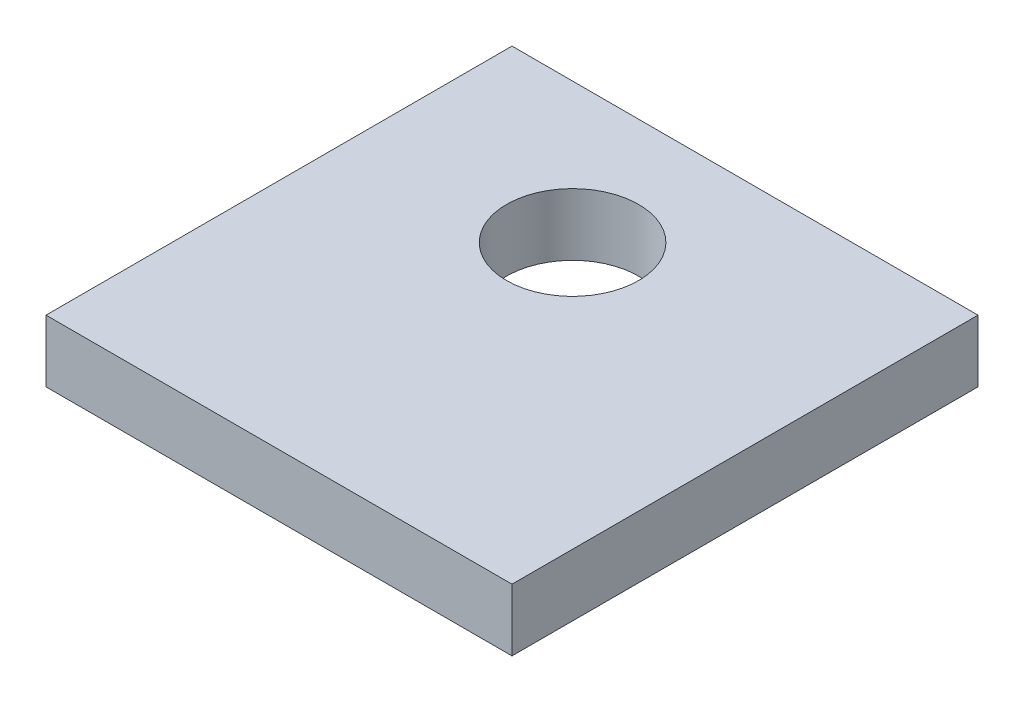
SolidWorks part; units mm, degrees
ref_plane "Front" through (0, 0, 0) normal (0, 0, 1) x (1, 0, 0)
ref_plane "Top" through (0, 0, 0) normal (0, 1, 0) x (1, 0, 0)
ref_plane "Right" through (0, 0, 0) normal (1, 0, 0) x (0, 0, -1)
sketch "Sketch1" plane through (0, 0, 0) normal (0, 1, 0) x (1, 0, 0)
  line L1 (-15, -15) -> (15, -15)
  line L2 (-15, -15) -> (-15, 15)
  line L3 (-15, 15) -> (15, 15)
  line L4 (15, -15) -> (15, 15)
  line L5 (-15, -15) -> (15, 15) construction
  line L6 (-15, 15) -> (15, -15) construction
  point P0 (0, 0)
  dimension "D1" = 30
  dimension "D2" = 30
extrude "Boss-Extrude1" add sketch "Sketch1" along normal mid plane 4
sketch "Sketch2" plane through (0, 2, 0) normal (0, 1, 0) x (1, 0, 0)
  circle A0 centre (-2.1, 6) radius 4.25
  circle A1 centre (-2.1, 6) radius 4 construction
  dimension "D1" = 8.5
extrude "Cut-Extrude1" cut sketch "Sketch2" against normal through all
